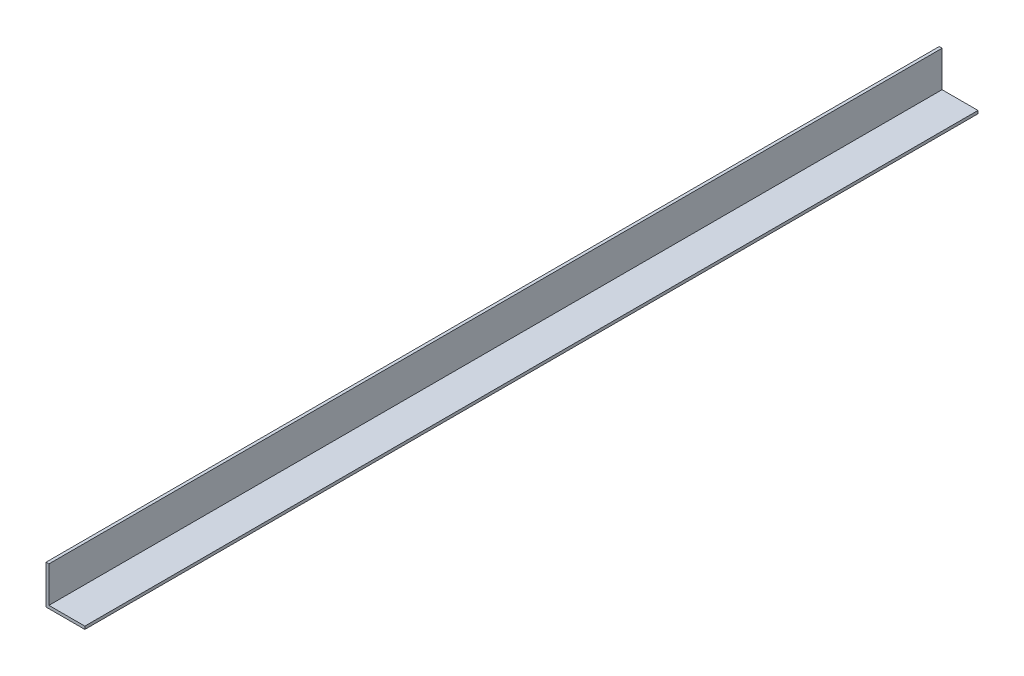
SolidWorks part; units mm, degrees
material "1060 Alloy"
ref_plane "xy" through (0, 0, 0) normal (0, 0, 1) x (1, 0, 0)
ref_plane "xz" through (0, 0, 0) normal (0, 1, 0) x (1, 0, 0)
ref_plane "yz" through (0, 0, 0) normal (1, 0, 0) x (0, 0, -1)
ref_axis "x" through (-88.99, 0, 0) along (1, 0, 0)
ref_axis "y" through (0, 55, 0) along (0, -1, 0)
ref_axis "z" through (0, 0, -88.99) along (0, 0, 1)
sketch "Sketch1" plane through (0, 0, 0) normal (0, 0, 1) x (1, 0, 0)
  line L0 (0, 0) -> (20, 0)
  line L1 (0, 0) -> (0, 20)
  dimension "D1" = 20
extrude "Extrude-Thin1" add sketch "Sketch1" along normal mid plane 460 thin thin type one direction wall 1.5
